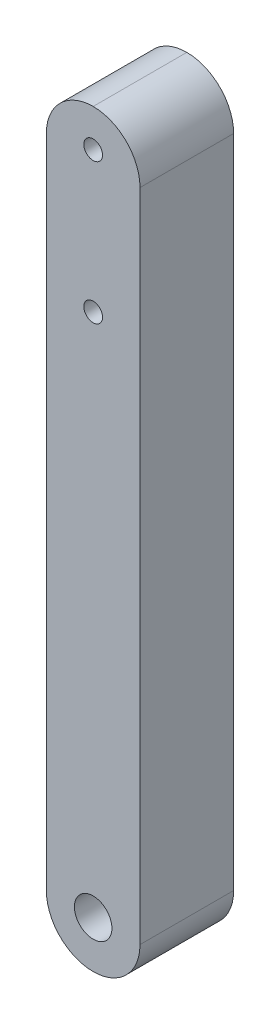
SolidWorks part; units mm, degrees
ref_plane "Front" through (0, 0, 0) normal (0, 0, 1) x (1, 0, 0)
ref_plane "Top" through (0, 0, 0) normal (0, 1, 0) x (1, 0, 0)
ref_plane "Right" through (0, 0, 0) normal (1, 0, 0) x (0, 0, -1)
sketch "Esquisse1" plane through (0, 0, 0) normal (0, 0, 1) x (1, 0, 0)
  line L1 (0, 0) -> (10, 0)
  line L2 (0, 0) -> (0, 80)
  line L3 (0, 80) -> (10, 80)
  line L4 (10, 0) -> (10, 80)
  dimension "D1" = 10
  dimension "D2" = 80
extrude "Boss.-Extru.1" add sketch "Esquisse1" along normal blind 10
sketch "Esquisse2" plane through (0, 0, 10) normal (0, 0, 1) x (1, 0, 0)
  line L0 (5, 80) -> (5, 61) construction
  line L1 (10, 80) -> (0, 80) construction
  line L2 (0, 0) -> (10, 0) construction
  line L3 (5, 5) -> (5, 0) construction
  circle A0 centre (5, 61) radius 1
  circle A1 centre (5, 76) radius 1
  circle A2 centre (5, 5) radius 2
  point P11 (5, 0)
  dimension "D1" = 15
  dimension "D2" = 4
  dimension "D3" = 2
  dimension "D4" = 4
  dimension "D5" = 5
extrude "Enlèv. mat.-Extru.1" cut sketch "Esquisse2" against normal up to vertex (10 mm away) up to point (0, 80, 0)
fillet "Congé1" radius 5 4 edges at (10, 80, 5) (0, 80, 5) (10, 0, 5) (0, 0, 5)
